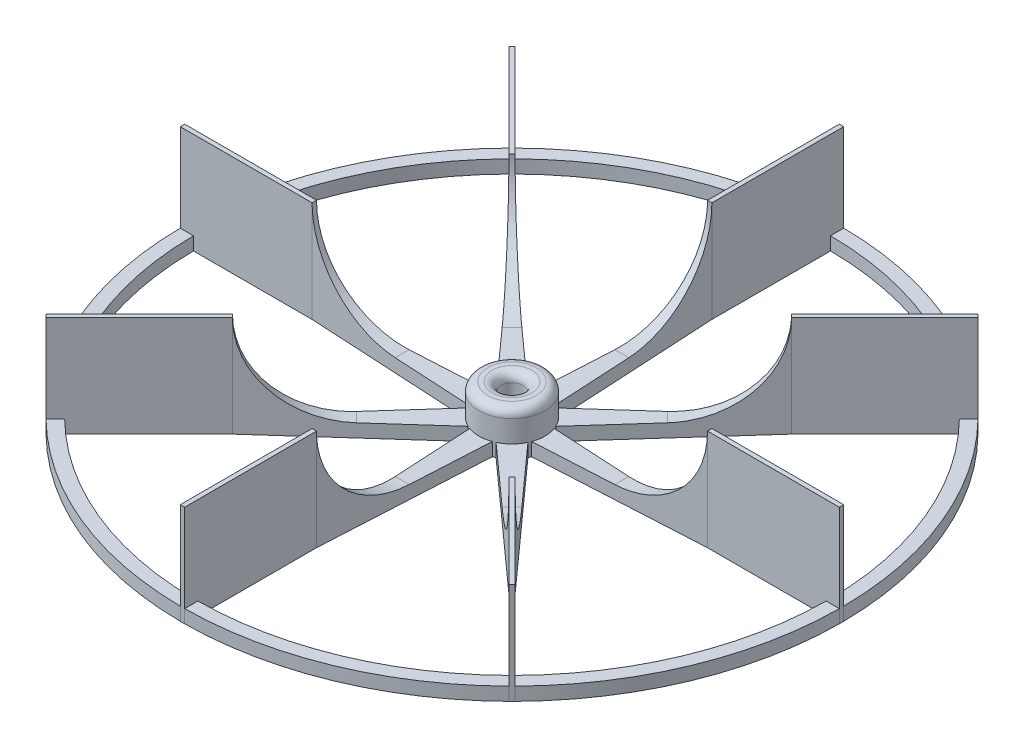
SolidWorks part; units mm, degrees
ref_plane "Front Plane" through (0, 0, 0) normal (0, 0, 1) x (1, 0, 0)
ref_plane "Top Plane" through (0, 0, 0) normal (0, 1, 0) x (1, 0, 0)
ref_plane "Right Plane" through (0, 0, 0) normal (1, 0, 0) x (0, 0, -1)
sketch "Sketch1" plane through (0, 0, 0) normal (0, 1, 0) x (1, 0, 0)
  line L0 (0, 9.525) -> (0, 76.2) construction
  line L1 (-0.635, 57.15) -> (-3.2577, 8.9506)
  line L2 (-0.635, 95.25) -> (0.635, 95.25)
  line L3 (-0.635, 95.25) -> (-0.635, 57.15)
  line L5 (0.635, 95.25) -> (0.635, 57.15)
  line L6 (-0.635, 95.25) -> (0.635, 57.15) construction
  line L7 (-0.635, 57.15) -> (0.635, 95.25) construction
  line L8 (-100, 100) -> (100, 100) construction
  line L9 (-100, 100) -> (-100, -100) construction
  line L10 (-100, -100) -> (100, -100) construction
  line L11 (100, 100) -> (100, -100) construction
  line L12 (-100, 100) -> (100, -100) construction
  line L13 (-100, -100) -> (100, 100) construction
  line L14 (0, 0) -> (-3.2577, 8.9506) construction
  line L15 (0, 0) -> (0, 9.525) construction
  line L16 (0.635, 57.15) -> (3.2577, 8.9506)
  circle A0 centre (0, 0) radius 76.2 construction
  circle A1 centre (0, 0) radius 9.525 construction
  arc A2 (3.2577, 8.9506) -> (-3.2577, 8.9506) centre (0, 0) ccw
  point P16 (-4.1722, 8.6177)
  point P17 (0, 12.9152)
  dimension "D1" = 19.05
  dimension "D2" = 152.4
  dimension "D3" = 1.27
  dimension "D4" = 38.1
  dimension "D5" = 200
  dimension "D6" = 200
  dimension "D7" = 20
extrude "Boss-Extrude1" add sketch "Sketch1" along normal blind 3.81
sketch "Sketch2" plane through (0, 3.81, 0) normal (0, 1, 0) x (1, 0, 0)
  line L1 (-0.635, 95.25) -> (0.635, 95.25)
  line L2 (-0.635, 95.25) -> (-0.635, 57.15)
  line L3 (-0.635, 57.15) -> (0.635, 57.15)
  line L4 (0.635, 95.25) -> (0.635, 57.15)
extrude "Boss-Extrude2" add sketch "Sketch2" along normal blind 25.4
fillet "Fillet1" radius 25.4 1 edges at (0, 3.81, -57.15)
sketch "Sketch3" plane through (0, 0, 0) normal (1, 0, 0) x (0, 0, -1)
  line L0 (0, 0) -> (0, 50000) construction
sketch "Sketch4" plane through (0, 0, 0) normal (0, 1, 0) x (1, 0, 0)
  circle A0 centre (0, 0) radius 3.175
  circle A1 centre (0, 0) radius 9.525
  arc A2 (3.2577, 8.9506) -> (-3.2577, 8.9506) centre (0, 0) ccw construction
  dimension "D1" = 6.35
extrude "Boss-Extrude3" add sketch "Sketch4" along normal blind 12.7
pattern_circular "CirPattern5" count 8 over 360 about axis through (0, 0, 0) along (0, 1, 0) of "Boss-Extrude1", "Boss-Extrude2", "Fillet1"
sketch "Sketch5" plane through (0, 0, 0) normal (0, 1, 0) x (1, 0, 0)
  line L0 (0.635, 95.25) -> (-0.635, 95.25) construction
  circle A0 centre (0, 0) radius 95.25
  circle A1 centre (0, 0) radius 91.44
  point P5 (0, 95.25)
  dimension "D1" = 3.81
extrude "Boss-Extrude4" add sketch "Sketch5" along normal blind 3.81
fillet "Fillet2" radius 2.54 2 edges at (0, 12.7, 3.175) (0, 12.7, 9.525)
